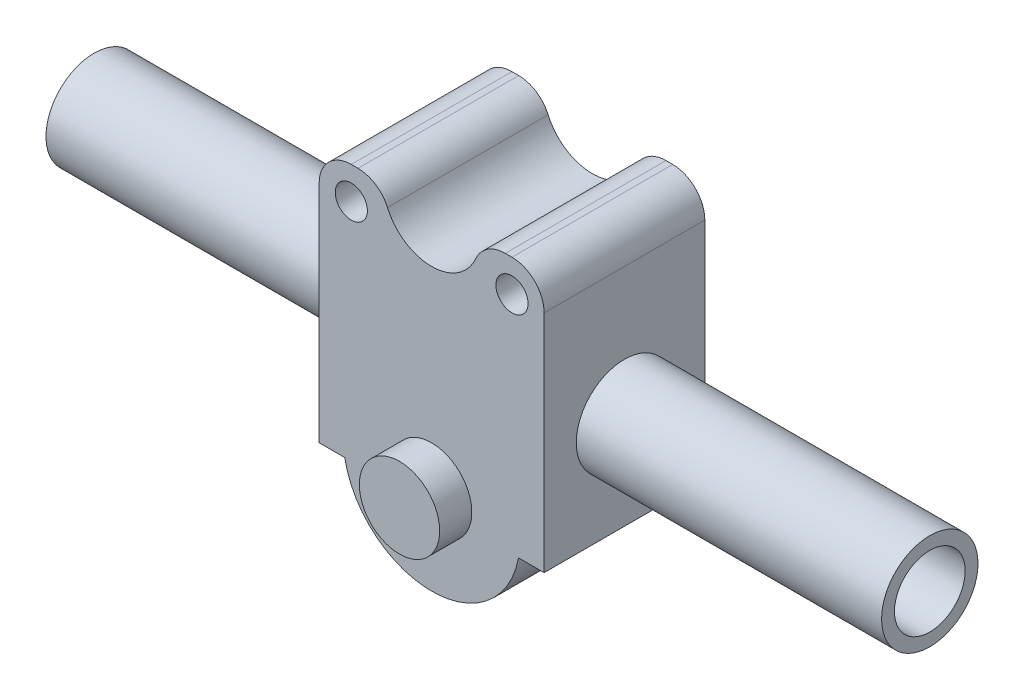
SolidWorks part; units mm, degrees
ref_plane "Front Plane" through (0, 0, 0) normal (0, 0, 1) x (1, 0, 0)
ref_plane "Top Plane" through (0, 0, 0) normal (0, 1, 0) x (1, 0, 0)
ref_plane "Right Plane" through (0, 0, 0) normal (1, 0, 0) x (0, 0, -1)
sketch "Sketch1" plane through (0, 0, 0) normal (0, 0, 1) x (1, 0, 0)
  line L0 (22.9129, 75) -> (25, 75)
  line L1 (-25, 75) -> (-22.9129, 75)
  line L2 (-35, 65) -> (-35, -5)
  line L3 (-35, -5) -> (-27.0416, -5)
  line L4 (35, 65) -> (35, -5)
  line L5 (27.0416, -5) -> (35, -5)
  arc A1 (-27.0416, -5) -> (27.0416, -5) centre (0, 0) ccw
  arc A2 (25, 75) -> (35, 65) centre (25, 65) cw
  arc A3 (-25, 75) -> (-35, 65) centre (-25, 65) ccw
  circle A4 centre (-25, 65) radius 5
  circle A5 centre (25, 65) radius 5
  arc A6 (-13.7477, 69) -> (13.7477, 69) centre (0, 75) ccw
  arc A7 (-13.7477, 69) -> (-22.9129, 75) centre (-22.9129, 65) ccw
  arc A8 (13.7477, 69) -> (22.9129, 75) centre (22.9129, 65) cw
  point P13 (35, 75)
  point P16 (-35, 75)
  point P23 (15, 75)
  dimension "D2" = 55
  dimension "D6" = 10
  dimension "D7" = 10
  dimension "D8" = 10
  dimension "D9" = 30
  dimension "D10" = 10
  dimension "D11" = 10
  dimension "D3" = 80
  dimension "D4" = 70
  dimension "D5" = 5
extrude "Boss-Extrude2" add sketch "Sketch1" along normal blind 50
shell "Shell2" thickness 5
sketch "Sketch3" plane through (0, 0, 0) normal (0, 0, -1) x (-1, 0, 0)
  circle A0 centre (0, 0) radius 15
  dimension "D1" = 30
extrude "Cut-Extrude1" cut sketch "Sketch3" against normal blind 5
sketch "Sketch4" plane through (0, 0, 0) normal (0, 0, -1) x (-1, 0, 0)
  circle A0 centre (0, 0) radius 6
  circle A1 centre (0, 0) radius 27.5
  dimension "D1" = 12
extrude "Boss-Extrude3" add sketch "Sketch4" along normal blind 10
sketch "Sketch5" plane through (35, 0, 0) normal (1, 0, 0) x (0, 0, -1)
  line L0 (0, -5) -> (0, 65) construction
  circle A0 centre (-25, 25) radius 15
  circle A1 centre (-25, 25) radius 11
  dimension "D1" = 30
  dimension "D2" = 22
  dimension "D3" = 25
  dimension "D4" = 25
extrude "Boss-Extrude4" add sketch "Sketch5" along normal blind 95
extrude "Cut-Extrude2" cut sketch "Sketch5<2>" against normal blind 80 contours A1 region at (35, 25, 25)
sketch "Sketch5<2>" plane through (35, 0, 0) normal (1, 0, 0) x (0, 0, -1) same geometry as "Sketch5"
extrude "Boss-Extrude5" add sketch "Sketch5<3>" against normal blind 95 from offset 70 offset against normal yes
sketch "Sketch5<3>" plane through (35, 0, 0) normal (1, 0, 0) x (0, 0, -1) same geometry as "Sketch5"
sketch "Sketch6" plane through (0, 0, 50) normal (0, 0, 1) x (1, 0, 0)
  circle A0 centre (0, 0) radius 6
  circle A1 centre (0, 0) radius 12.5
  dimension "D1" = 12
  dimension "D2" = 25
extrude "Boss-Extrude6" add sketch "Sketch6" along normal blind 5
extrude "Cut-Extrude3" cut sketch "Sketch6<2>" against normal blind 5 contours A0 region at (0, 0, 50)
sketch "Sketch6<2>" plane through (0, 0, 50) normal (0, 0, 1) x (1, 0, 0) same geometry as "Sketch6"
extrude "Boss-Extrude7" add sketch "Sketch6<3>" against normal blind 38 contours A1 A0 region at (-12.1464, 0, 50)
sketch "Sketch6<3>" plane through (0, 0, 50) normal (0, 0, 1) x (1, 0, 0) same geometry as "Sketch6"
extrude "Boss-Extrude8" add sketch "Sketch6<4>" along normal blind 10 contours A0 | A1 A0 region at (0, 0, 50) region at (-12.1464, 0, 50)
sketch "Sketch6<4>" plane through (0, 0, 50) normal (0, 0, 1) x (1, 0, 0) same geometry as "Sketch6"
